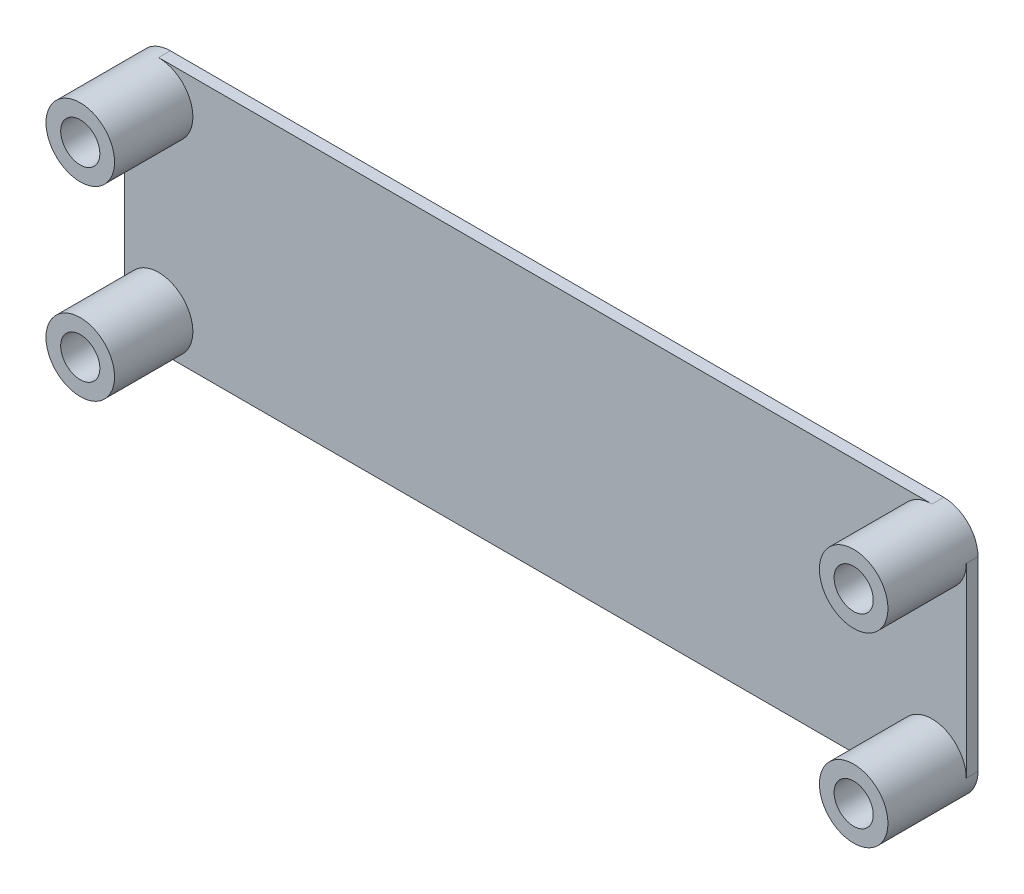
SolidWorks part; units mm, degrees
ref_plane "Спереди" through (0, 0, 0) normal (0, 0, 1) x (1, 0, 0)
ref_plane "Сверху" through (0, 0, 0) normal (0, 1, 0) x (1, 0, 0)
ref_plane "Справа" through (0, 0, 0) normal (1, 0, 0) x (0, 0, -1)
sketch "Эскиз1" plane through (0, 0, 0) normal (0, 0, 1) x (1, 0, 0)
  line L1 (0, 0) -> (86, 0)
  line L2 (0, 0) -> (0, 26)
  line L3 (0, 26) -> (86, 26)
  line L4 (86, 0) -> (86, 26)
  circle A0 centre (82.5, 22.5) radius 3.5
  circle A1 centre (82.5, 3.5) radius 3.5
  circle A2 centre (3.5, 22.5) radius 3.5
  circle A3 centre (3.5, 3.5) radius 3.5
  point P11 (86, 13)
  point P12 (43, 26)
  point P15 (0, 0)
  point P16 (0, 0)
  point P17 (0, 0)
  point P18 (0, 0)
  dimension "D1" = 86
  dimension "D2" = 26
  dimension "D3" = 19
  dimension "D4" = 79
  dimension "D5" = 9.5
  dimension "D6" = 39.5
extrude "Бобышка-Вытянуть1" add sketch "Эскиз1" along normal blind 1.2 contours A3 L1 A1 L4 A0 L3 A2 L2 | A2 | A3 | A0 | A1 region at (43, 13, 0) region at (3.5, 3.5, 0) region at (82.5, 3.5, 0) region at (3.5, 22.5, 0) region at (82.5, 22.5, 0)
extrude "Бобышка-Вытянуть2" add sketch "Эскиз1<3>" along normal blind 8 from surface contours A2 | A3 | A0 | A1 starting at face at (43, 13, 1.2)
sketch "Эскиз1<3>" plane through (0, 0, 0) normal (0, 0, 1) x (1, 0, 0) same geometry as "Эскиз1"
sketch "Эскиз2" plane through (0, 0, 9.2) normal (0, 0, 1) x (1, 0, 0)
  circle A0 centre (3.5, 22.5) radius 2
  circle A1 centre (3.5, 3.5) radius 2
  circle A2 centre (82.5, 22.5) radius 2
  circle A3 centre (82.5, 3.5) radius 2
  dimension "D1" = 4
  dimension "D2" = 4
  dimension "D3" = 4
  dimension "D4" = 4
extrude "Вырез-Вытянуть1" cut sketch "Эскиз2" against normal blind 6
